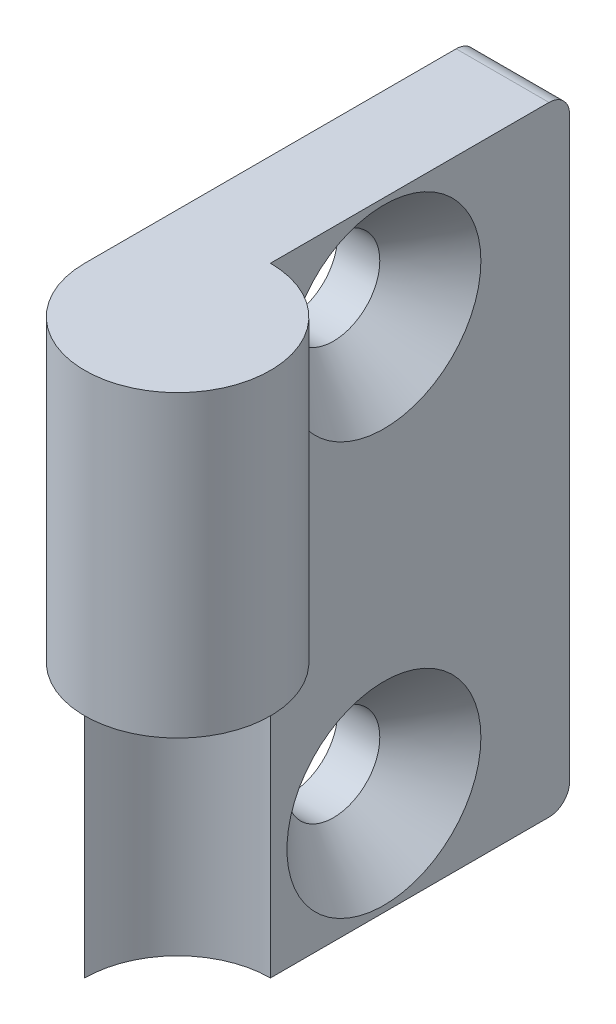
SolidWorks part; units mm, degrees
material "Brass"
ref_plane "Front Plane" through (0, 0, 0) normal (0, 0, 1) x (1, 0, 0)
ref_plane "Top Plane" through (0, 0, 0) normal (0, 1, 0) x (1, 0, 0)
ref_plane "Right Plane" through (0, 0, 0) normal (1, 0, 0) x (0, 0, -1)
sketch "Sketch1" plane through (0, 0, 0) normal (1, 0, 0) x (0, 0, -1)
  line L1 (0, 0) -> (19, 0)
  line L2 (0, 0) -> (0, 30)
  line L3 (0, 30) -> (19, 30)
  line L4 (19, 0) -> (19, 30)
  dimension "D1" = 19
  dimension "D2" = 30
extrude "Plate" add sketch "Sketch1" along normal blind 4.5
sketch "Sketch2" plane through (0, 30, 0) normal (0, 1, 0) x (1, 0, 0)
  circle A0 centre (4.5, 0) radius 4.5
extrude "Cylinder" add sketch "Sketch2" against normal blind 14.5
extrude "Clearance" cut sketch "Sketch2<2>" along normal up to surface (-14.5 mm away) from vertex up to face at (4.8107, 15.5, 0.3107) starting at point (4.5, 0, 0)
sketch "Sketch2<2>" plane through (0, 30, 0) normal (0, 1, 0) x (1, 0, 0) same geometry as "Sketch2"
fillet "Fillet1" radius 1 2 edges at (2.25, 0, -19) (2.25, 30, -19)
hole_wizard "CSK for M4 Countersunk Flat Head Screw1" positions "Sketch3" profile "Sketch4" countersink size "M4" standard "ISO" end condition up to next
sketch "Sketch3" plane through (4.5, 0, 0) normal (1, 0, 0) x (0, 0, -1)
  line L0 (0, 15.5) -> (0, 0) construction
  line L1 (4.5, 0) -> (18, 0) construction
  point P0 (10, 25)
  point P2 (10, 5)
  point P7 (0, 0)
  dimension "D1" = 10
  dimension "D2" = 20
  dimension "D3" = 5
sketch "Sketch4" plane through (4.5, 25, -10) normal (0, 1, 0) x (0, 0, -1)
  line L0 (0, 0) -> (0, 4.5)
  line L1 (0, 4.5) -> (2.25, 4.5)
  line L2 (2.25, 4.5) -> (2.25, 2.45)
  line L3 (2.25, 2.45) -> (4.7, 0)
  line L5 (4.7, 0) -> (0, 0)
  line L6 (-2.25, 2.45) -> (-4.7, 0) construction
  line L11 (0, -6.35) -> (0, 107.95) construction
  dimension "Thru Hole Dia." = 4.5
  dimension "Thru Hole Depth" = 4.5
  dimension "Near C'Sink Dia." = 9.4
  dimension "Near C'Sink Angle" = 90
